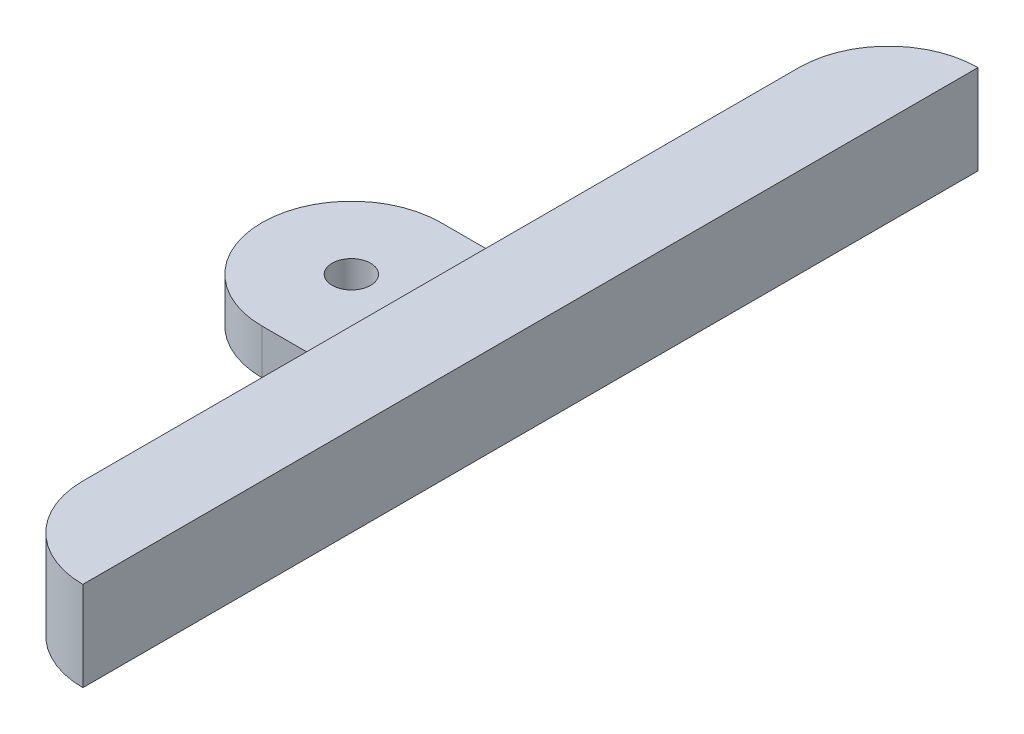
SolidWorks part; units mm, degrees
ref_plane "Plan de face" through (0, 0, 0) normal (0, 0, 1) x (1, 0, 0)
ref_plane "Plan de dessus" through (0, 0, 0) normal (0, 1, 0) x (1, 0, 0)
ref_plane "Plan de droite" through (0, 0, 0) normal (1, 0, 0) x (0, 0, -1)
sketch "Sketch1" plane through (0, 0, 0) normal (0, 1, 0) x (1, 0, 0)
  line L0 (0, 50) -> (0, -50)
  line L1 (-10, 50) -> (0, 50)
  line L2 (-10, 50) -> (-10, -50)
  line L3 (-10, -50) -> (0, -50)
  line L5 (-10, 50) -> (0, 0) construction
  line L6 (-10, -50) -> (0, 0) construction
  point P0 (0, 0)
  dimension "D1" = 10
extrude "Boss-Extrude1" add sketch "Sketch1" along normal blind 5
sketch "Sketch2" plane through (0, 5, 0) normal (0, 1, 0) x (1, 0, 0)
  line L10 (-10, 50) -> (0, 50)
  line L11 (-10, 50) -> (-10, -50)
  line L12 (-10, -50) -> (0, -50)
  line L13 (0, 50) -> (0, -50)
extrude "Boss-Extrude2" add sketch "Sketch2" along normal blind 5
sketch "Sketch3" plane through (-10, 0, 0) normal (-1, 0, 0) x (0, 0, 1)
  line L0 (0, 30) -> (0, -20) construction
  line L3 (-10, 5) -> (10, 5)
  line L4 (10, 5) -> (10, 0)
  line L5 (10, 0) -> (-10, 0)
  line L6 (-10, 0) -> (-10, 5)
  point P9 (0, 5)
  dimension "D1" = 20
  dimension "D2" = 30
extrude "Boss-Extrude3" add sketch "Sketch3" along normal blind 20
fillet "Fillet1" radius 10 2 edges at (-30, 2.5, 10) (-30, 2.5, -10)
sketch "Sketch4" plane through (0, 5, 0) normal (0, 1, 0) x (1, 0, 0)
  circle A0 centre (-20, 0) radius 2.15
  dimension "D1" = 4.3
extrude "Cut-Extrude1" cut sketch "Sketch4" against normal up to next
fillet "Fillet2" radius 10 2 edges at (-10, 5, -50) (-10, 5, 50)
